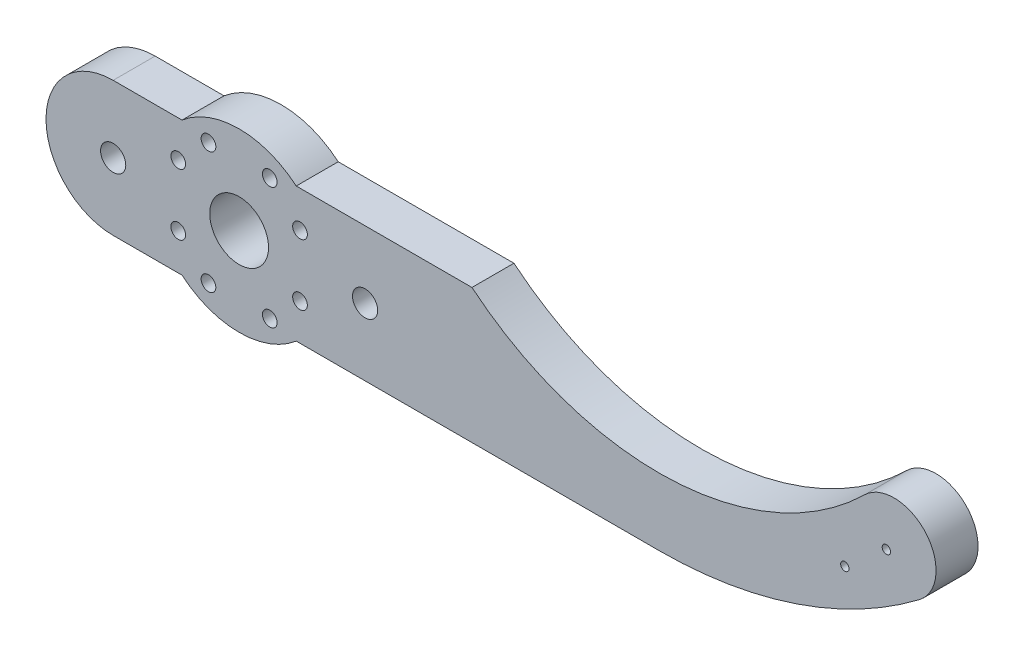
SolidWorks part; units mm, degrees
ref_plane "Plan de face" through (0, 0, 0) normal (0, 0, 1) x (1, 0, 0)
ref_plane "Plan de dessus" through (0, 0, 0) normal (0, 1, 0) x (1, 0, 0)
ref_plane "Plan de droite" through (0, 0, 0) normal (1, 0, 0) x (0, 0, -1)
sketch "Esquisse1" plane through (0, 0, 0) normal (0, 0, 1) x (1, 0, 0)
  line L0 (0, 0) -> (80, 0) construction
  line L1 (20, 0) -> (20, 23.8674) construction
  line L2 (0, 0) -> (0, 35) construction
  line L3 (0, 35) -> (50, 35) construction
  line L4 (6.8007, 8) -> (20, 8)
  line L5 (74.5, 10.005) -> (78, 6.4343) construction
  line L6 (20, 8) -> (27.7289, 8)
  line L7 (6.8007, -8) -> (50, -8)
  line L8 (50, 35) -> (50, -8) construction
  line L10 (0, 0) -> (-15, 0) construction
  line L12 (78, 6.4343) -> (77.0843, 5.6542) construction
  line L13 (72.1363, 1.4391) -> (77.0843, 5.6542) construction
  line L14 (0, 0) -> (7.25, 0) construction
  line L15 (7.25, 0) -> (7.25, 3.65) construction
  line L16 (-6.8007, 8) -> (-15, 8)
  line L17 (-6.8007, -8) -> (-15, -8)
  circle A0 centre (77.0843, 5.6542) radius 0.5
  arc A1 (0, 8) -> (0, -8) centre (0, 0) ccw construction
  circle A2 centre (50, 35) radius 35 construction
  arc A3 (27.7289, 8) -> (74.5, 10.005) centre (50, 35) ccw
  arc A4 (74.5, 10.005) -> (81.0259, 2.4538) centre (78, 6.4343) cw
  arc A5 (50, -8) -> (81.0259, 2.4538) centre (50, 43.2677) ccw
  circle A6 centre (15, 0) radius 1.5
  arc A7 (-15, 8) -> (-15, -8) centre (-15, 0) ccw
  circle A8 centre (-15, 0) radius 1.5
  circle A9 centre (0, 0) radius 3.5
  circle A10 centre (72.1363, 1.4391) radius 0.5
  arc A11 (-6.8007, 8) -> (6.8007, 8) centre (0, 0) cw
  arc A12 (6.8007, -8) -> (-6.8007, -8) centre (0, 0) cw
  circle A13 centre (7.25, 3.65) radius 0.875
  circle A14 centre (7.25, -3.65) radius 0.875
  circle A15 centre (3.65, -7.25) radius 0.875
  circle A16 centre (-3.65, -7.25) radius 0.875
  circle A17 centre (-7.25, -3.65) radius 0.875
  circle A18 centre (-7.25, 3.65) radius 0.875
  circle A19 centre (-3.65, 7.25) radius 0.875
  circle A20 centre (3.65, 7.25) radius 0.875
  point P52 (0, 0)
  dimension "D3" = 3
  dimension "D4" = 35
  dimension "D6" = 70
  dimension "D7" = 5
  dimension "D8" = 8
  dimension "D9" = 28
  dimension "D10" = 15
  dimension "D11" = 8
  dimension "D13" = 3
  dimension "D14" = 7
  dimension "D15" = 1.2
  dimension "D17" = 1
  dimension "D18" = 6.5
  dimension "D19" = 10.5
  dimension "D20" = 1.75
  dimension "D1" = 20
  dimension "D2" = 80
  dimension "D5" = 50
  dimension "D12" = 15
  dimension "D16" = 86
  dimension "D21" = 3.65
  dimension "D22" = 7.25
  dimension "D23" = 4
extrude "Boss.-Extru.1" add sketch "Esquisse1" along normal blind 5
